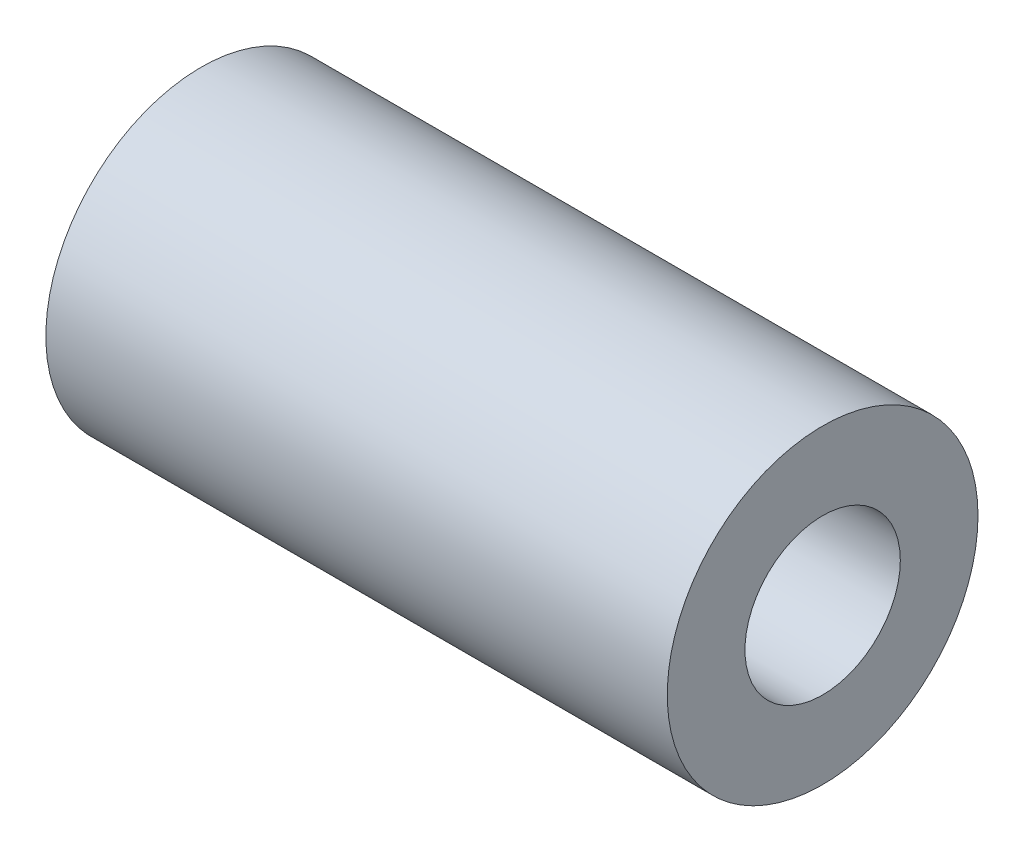
SolidWorks part; units mm, degrees
ref_plane "Front" through (0, 0, 0) normal (0, 0, 1) x (1, 0, 0)
ref_plane "Top" through (0, 0, 0) normal (0, 1, 0) x (1, 0, 0)
ref_plane "Right" through (0, 0, 0) normal (1, 0, 0) x (0, 0, -1)
ref_axis "Axis1" through (-84.4107, 0, 0) along (1, 0, 0)
ref_axis "Axis2" through (0, 64.3378, 0) along (0, -1, 0)
ref_axis "Axis3" through (0, 0, -102.329) along (0, 0, 1)
sketch "Sketch1" plane through (0, 0, 0) normal (0, 0, 1) x (1, 0, 0)
  line L0 (0, 0) -> (-148.643, 0) construction
  line L2 (-140.4561, 50) -> (59.5439, 50)
  line L3 (-140.4561, 50) -> (-140.4561, 25)
  line L4 (-140.4561, 25) -> (59.5439, 25)
  line L5 (59.5439, 50) -> (59.5439, 25)
  dimension "D1" = 50
  dimension "D2" = 200
  dimension "D3" = 100
revolve "Revolve1" add sketch "Sketch1" angle 360 about L0
